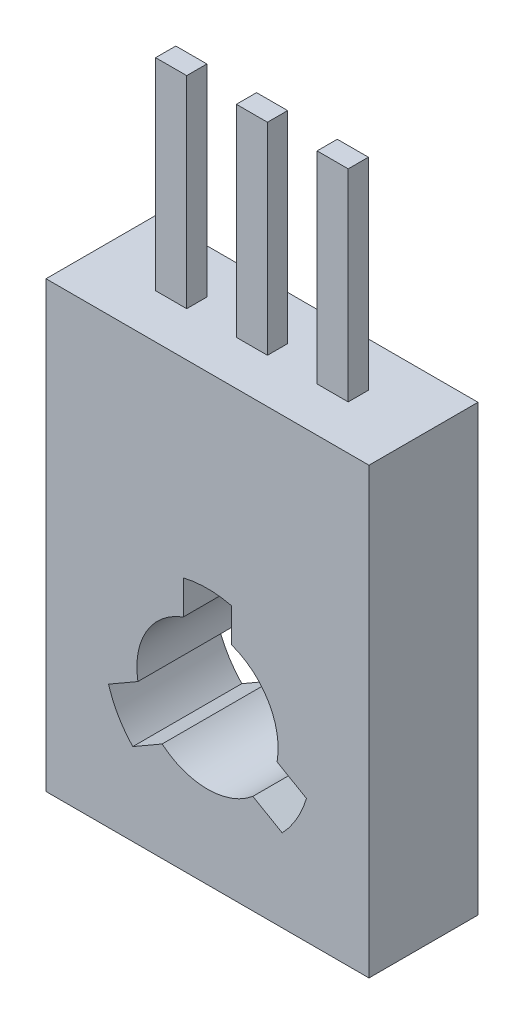
SolidWorks part; units mm, degrees
ref_plane "Front Plane" through (0, 0, 0) normal (0, 0, 1) x (1, 0, 0)
ref_plane "Top Plane" through (0, 0, 0) normal (0, 1, 0) x (1, 0, 0)
ref_plane "Right Plane" through (0, 0, 0) normal (1, 0, 0) x (0, 0, -1)
sketch "Sketch1" plane through (0, 0, 0) normal (0, 0, 1) x (1, 0, 0)
  line L1 (-4, 5.5) -> (4, 5.5)
  line L2 (-4, 5.5) -> (-4, -5.5)
  line L3 (-4, -5.5) -> (4, -5.5)
  line L4 (4, 5.5) -> (4, -5.5)
  line L5 (-4, 5.5) -> (4, -5.5) construction
  line L6 (-4, -5.5) -> (4, 5.5) construction
  circle A0 centre (0, -1.7) radius 2.555
  point P0 (0, 0)
  dimension "D3" = 5.11
  dimension "D1" = 11
  dimension "D2" = 8
  dimension "D4" = 3.8
extrude "Boss-Extrude1" add sketch "Sketch1" along normal mid plane 2.7
sketch "Sketch2" plane through (0, 5.5, 0) normal (0, 1, 0) x (1, 0, 0)
  line L0 (0, 0.8819) -> (0, -0.7814) construction
  line L1 (-0.385, 0.25) -> (0.385, 0.25)
  line L2 (-0.385, 0.25) -> (-0.385, -0.25)
  line L3 (-0.385, -0.25) -> (0.385, -0.25)
  line L4 (0.385, 0.25) -> (0.385, -0.25)
  line L5 (-0.385, 0.25) -> (0.385, -0.25) construction
  line L6 (-0.385, -0.25) -> (0.385, 0.25) construction
  line L7 (-2.385, 0.25) -> (-1.615, 0.25)
  line L8 (-2.385, 0.25) -> (-2.385, -0.25)
  line L9 (-2.385, -0.25) -> (-1.615, -0.25)
  line L10 (-1.615, 0.25) -> (-1.615, -0.25)
  line L11 (-2.385, 0.25) -> (-1.615, -0.25) construction
  line L12 (-2.385, -0.25) -> (-1.615, 0.25) construction
  line L13 (2.385, -0.25) -> (1.615, -0.25)
  line L14 (1.615, 0.25) -> (1.615, -0.25)
  line L15 (2.385, 0.25) -> (1.615, 0.25)
  line L16 (2.385, 0.25) -> (2.385, -0.25)
  point P0 (0, 0)
  point P7 (-2, 0)
  dimension "D1" = 0.5
  dimension "D2" = 0.77
  dimension "D3" = 0.77
  dimension "D4" = 0.5
  dimension "D5" = 2
extrude "Boss-Extrude2" add sketch "Sketch2" along normal blind 5
sketch "Sketch4" plane through (0, 0, 1.35) normal (0, 0, 1) x (1, 0, 0)
  line L0 (0, 0.8936) -> (0, -1.7) construction
  line L3 (-0.6, 0.8232) -> (-0.6, -0.0561)
  line L4 (0.6, 0.8232) -> (0.6, -0.0561)
  line L5 (2.4852, -2.442) -> (1.7237, -2.0023)
  line L6 (1.8852, -3.4812) -> (1.1237, -3.0416)
  line L7 (-1.8852, -3.4812) -> (-1.1237, -3.0416)
  line L8 (-2.4852, -2.442) -> (-1.7237, -2.0023)
  arc A0 (-1.1237, -3.0416) -> (1.1237, -3.0416) centre (0, -1.7) ccw
  arc A1 (-1.8852, -3.4812) -> (1.8852, -3.4812) centre (0, -1.7) ccw
  arc A2 (-0.6, -0.0561) -> (-1.7237, -2.0023) centre (0, -1.7) ccw
  arc A3 (-0.6, 0.8232) -> (-2.4852, -2.442) centre (0, -1.7) ccw
  arc A4 (1.7237, -2.0023) -> (0.6, -0.0561) centre (0, -1.7) ccw
  arc A5 (2.4852, -2.442) -> (0.6, 0.8232) centre (0, -1.7) ccw
  point P22 (0, -1.7)
  dimension "D1" = 3.5
  dimension "D2" = 0.6
  dimension "D3" = 3
extrude "Boss-Extrude3" add sketch "Sketch4" against normal up to surface (2.7 mm away) up to face at (0, 0, -1.35)
